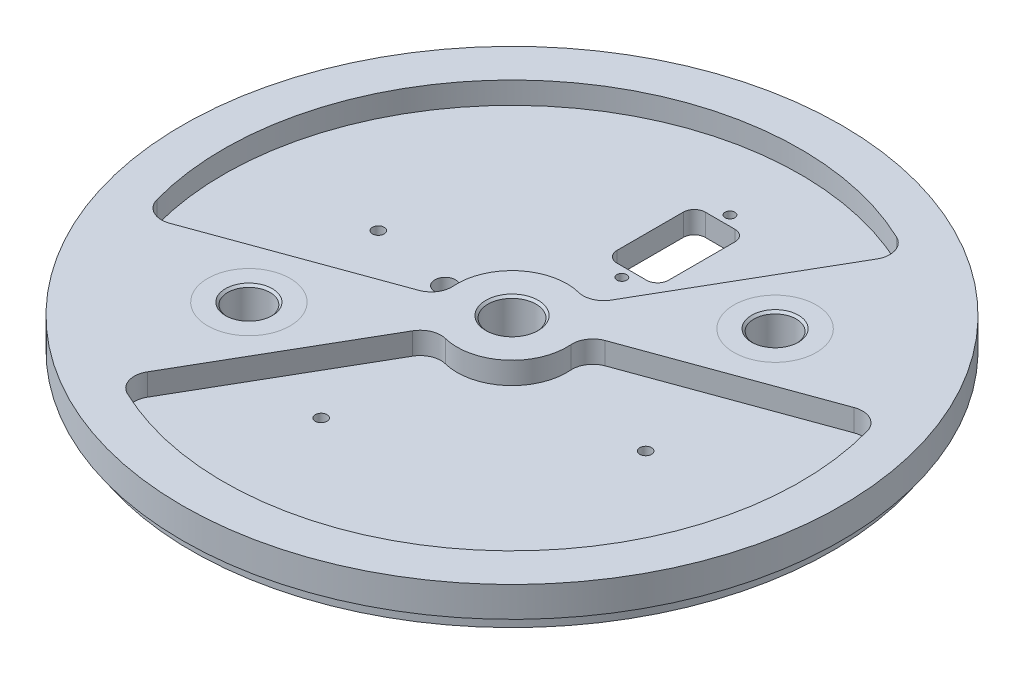
SolidWorks part; units mm, degrees
material "Delrin 2700 NC010, Low Viscosity Acetal Copolymer (SS)"
ref_plane "Front Plane" through (0, 0, 0) normal (0, 0, 1) x (1, 0, 0)
ref_plane "Top Plane" through (0, 0, 0) normal (0, 1, 0) x (1, 0, 0)
ref_plane "Right Plane" through (0, 0, 0) normal (1, 0, 0) x (0, 0, -1)
sketch "Sketch1" plane through (0, 0, 0) normal (0, 1, 0) x (1, 0, 0)
  circle A0 centre (0, 0) radius 76.2
  dimension "D1" = 152.4
extrude "Boss-Extrude1" add sketch "Sketch1" along normal blind 10.16
hole_wizard "Tap Drill for #4-40 Tap1" positions "Sketch3" profile "Sketch4" hole size "#4-40" standard "ANSI Inch" end condition through all
sketch "Sketch3" plane through (0, 0, 0) normal (0, -1, 0) x (-1, 0, 0)
  point P0 (0, 25.4)
  point P2 (0, 50.4)
  dimension "D1" = 25.4
  dimension "D2" = 25
sketch "Sketch4" plane through (0, 0, -25.4) normal (1, 0, 0) x (0, 0, -1)
  line L0 (0, 0) -> (0, 10.16)
  line L1 (0, 10.16) -> (1.1303, 10.16)
  line L2 (1.1303, 10.16) -> (1.1303, 0)
  line L5 (1.1303, 0) -> (0, 0)
  line L11 (0, -6.35) -> (0, 107.95) construction
  dimension "Thru Hole Dia." = 2.2606
  dimension "Thru Hole Depth" = 10.16
sketch "Sketch2" plane through (0, 0, 0) normal (0, -1, 0) x (1, 0, 0)
  line L0 (0, 0) -> (0, -55.372) construction
  line L1 (-3.429, -27.686) -> (3.429, -27.686)
  line L2 (-5.969, -30.226) -> (-5.969, -45.574)
  line L3 (-3.429, -48.114) -> (3.429, -48.114)
  line L4 (5.969, -30.226) -> (5.969, -45.574)
  arc A0 (3.429, -48.114) -> (5.969, -45.574) centre (3.429, -45.574) ccw
  arc A1 (-5.969, -45.574) -> (-3.429, -48.114) centre (-3.429, -45.574) ccw
  arc A2 (3.429, -27.686) -> (5.969, -30.226) centre (3.429, -30.226) cw
  arc A3 (-3.429, -27.686) -> (-5.969, -30.226) centre (-3.429, -30.226) ccw
  circle A4 centre (0, -25.4) radius 1.1303 construction
  circle A5 centre (0, -50.4) radius 1.1303 construction
  point P10 (5.969, -27.686)
  point P13 (-5.969, -27.686)
  point P17 (0, -27.686)
  dimension "D2" = 2.54
  dimension "D1" = 11.938
  dimension "D3" = 2.286
  dimension "D4" = 2.286
extrude "Cut-Extrude1" cut sketch "Sketch2" against normal through all
hole_wizard "Tap Drill for #6-32 Tap1" positions "Sketch5" profile "Sketch6" hole size "#6-32" standard "ANSI Inch" end condition through all
sketch "Sketch5" plane through (0, 0, 0) normal (0, -1, 0) x (-1, 0, 0)
  line L0 (0, 0) -> (58.3519, 0) construction
  line L2 (0, 0) -> (37.5212, 6.616) construction
  point P0 (37.5212, 6.616)
  dimension "D1" = 10
  dimension "D2" = 38.1
sketch "Sketch6" plane through (-37.5212, 0, -6.616) normal (1, 0, 0) x (0, 0, -1)
  line L0 (0, 0) -> (0, 10.16)
  line L1 (0, 10.16) -> (1.3525, 10.16)
  line L2 (1.3525, 10.16) -> (1.3525, 0)
  line L5 (1.3525, 0) -> (0, 0)
  line L11 (0, -6.35) -> (0, 107.95) construction
  dimension "Thru Hole Dia." = 2.7051
  dimension "Thru Hole Depth" = 10.16
pattern_circular "CirPattern1" count 4 over 360 about axis through (0, 0, 0) along (0, 1, 0) skipping 3 of "Tap Drill for #6-32 Tap1"
hole_wizard "W (0.386) Diameter Hole1" positions "Sketch7" profile "Sketch8" hole size "W" standard "ANSI Inch" end condition through all
sketch "Sketch7" plane through (0, 0, 0) normal (0, -1, 0) x (-1, 0, 0)
  line L2 (0, 0) -> (-33.0778, 27.7556) construction
  line L4 (0, 0) -> (0, 19.4817) construction
  point P0 (-33.0778, 27.7556)
  point P17 (33.0778, -27.7556)
  dimension "D1" = 50
  dimension "D2" = 43.18
  dimension "D3" = 43.18
sketch "Sketch8" plane through (33.0778, 0, -27.7556) normal (1, 0, 0) x (0, 0, -1)
  line L0 (0, 0) -> (0, 10.16)
  line L1 (0, 10.16) -> (4.9022, 10.16)
  line L2 (4.9022, 10.16) -> (4.9022, 0)
  line L5 (4.9022, 0) -> (0, 0)
  line L11 (0, -6.35) -> (0, 107.95) construction
  dimension "Thru Hole Dia." = 9.8044
  dimension "Thru Hole Depth" = 10.16
hole_wizard "3/16 (0.1875) Diameter Hole1" positions "Sketch10" profile "Sketch11" hole size "3/16" standard "ANSI Inch" end condition through all
sketch "Sketch10" plane through (0, 0, 0) normal (0, -1, 0) x (-1, 0, 0)
  line L0 (0, 0) -> (37.5212, 6.616) construction
  point P0 (18.7606, 3.308)
sketch "Sketch11" plane through (-18.7606, 0, -3.308) normal (1, 0, 0) x (0, 0, -1)
  line L0 (0, 0) -> (0, 10.16)
  line L1 (0, 10.16) -> (2.3812, 10.16)
  line L2 (2.3812, 10.16) -> (2.3812, 0)
  line L5 (2.3812, 0) -> (0, 0)
  line L11 (0, -6.35) -> (0, 107.95) construction
  dimension "Thru Hole Dia." = 4.7625
  dimension "Thru Hole Depth" = 10.16
sketch "Sketch12" plane through (0, 0, 0) normal (0, -1, 0) x (1, 0, 0)
  line L0 (0, 0) -> (31.6547, 37.7246) construction
  line L10 (19.8869, 28.7385) -> (24.8486, 24.5751)
  line L11 (19.8869, 28.7385) -> (6.4989, 12.7833)
  line L12 (6.4989, 12.7833) -> (11.4606, 8.62)
  line L13 (24.8486, 24.5751) -> (11.4606, 8.62)
  line L17 (0, 0) -> (-53.1972, 0) construction
  line L18 (-33.0778, 27.7556) -> (33.0778, -27.7556) construction
  circle A0 centre (22.3677, 26.6568) radius 3.2385
  circle A1 centre (8.9797, 10.7016) radius 3.2385
  circle A2 centre (33.0778, -27.7556) radius 4.9022 construction
  circle A3 centre (-33.0778, 27.7556) radius 4.9022 construction
  circle A4 centre (33.0778, -27.7556) radius 4.9022
  circle A5 centre (-33.0778, 27.7556) radius 4.9022
  dimension "D1" = 6.477
  dimension "D2" = 13.97
  dimension "D3" = 20.828
extrude "Cut-Extrude4" cut sketch "Sketch12" against normal blind 3.175 contours A1 L13 A0 L11 | L10 A0 | L12 A1 | L12 A1 | L10 A0 region at (23.2512, 0, 27.7097) region at (15.6737, 0, 18.6792) region at (21.4842, 0, 25.6039) region at (9.8632, 0, 11.7545) region at (8.0963, 0, 9.6487)
ref_plane "Plane1" through (0, 0, 0) normal (0.6428, 0, 0.766) x (0.766, 0, -0.6428)
mirror "Mirror1" about plane through (0, 0, 0) normal (0.6428, 0, 0.766) of "Cut-Extrude4"
hole_wizard "7/16 (0.4375) Diameter Hole1" positions "Sketch13" profile "Sketch14" hole size "7/16" standard "ANSI Inch" end condition through all
sketch "Sketch13" plane through (0, 0, 0) normal (0, -1, 0) x (-1, 0, 0)
  point P0 (0, 0)
sketch "Sketch14" plane through (0, 0, 0) normal (1, 0, 0) x (0, 0, -1)
  line L0 (0, 0) -> (0, 10.16)
  line L1 (0, 10.16) -> (5.5562, 10.16)
  line L2 (5.5562, 10.16) -> (5.5562, 0)
  line L5 (5.5562, 0) -> (0, 0)
  line L11 (0, -6.35) -> (0, 107.95) construction
  dimension "Thru Hole Dia." = 11.1125
  dimension "Thru Hole Depth" = 10.16
sketch "Sketch15" plane through (0, 0, 0) normal (0, -1, 0) x (1, 0, 0)
  circle A0 centre (0, 0) radius 74.041
  circle A1 centre (0, 0) radius 76.2 construction
  circle A2 centre (0, 0) radius 76.2
  dimension "D1" = 148.082
extrude "Cut-Extrude5" cut sketch "Sketch15" against normal blind 3.175
sketch "Sketch17" plane through (0, 10.16, 0) normal (0, 1, 0) x (1, 0, 0)
  circle A0 centre (-33.0778, -27.7556) radius 9.525
  circle A1 centre (33.0778, 27.7556) radius 9.525
  dimension "D1" = 19.05
  dimension "D2" = 19.05
split line "Split Line1"
sketch "Sketch19" plane through (0, 0, 0) normal (0, -1, 0) x (1, 0, 0)
  circle A0 centre (-33.0778, 27.7556) radius 9.525
  circle A1 centre (33.0778, -27.7556) radius 9.525
  dimension "D1" = 19.05
  dimension "D2" = 19.05
split line "Split Line2"
chamfer "Chamfer2" distance 0.508 angle 45 6 edges at (-33.0778, 0, 22.8534) (33.0778, 0, -32.6578) (-33.0778, 10.16, 22.8534) (33.0778, 10.16, -32.6578) (0, 0, -5.5562) (0, 10.16, -5.5562)
sketch "Sketch18" plane through (0, 10.16, 0) normal (0, 1, 0) x (1, 0, 0)
  circle A0 centre (0, 0) radius 76.2 construction
  circle A1 centre (33.0778, 27.7556) radius 9.525 construction
  circle A2 centre (-33.0778, -27.7556) radius 9.525 construction
  circle A3 centre (0, 0) radius 76.2
  circle A4 centre (33.0778, 27.7556) radius 9.525
  circle A5 centre (-33.0778, -27.7556) radius 9.525
  circle A7 centre (0, 0) radius 12.7
  circle A8 centre (-18.7606, 3.308) radius 9.525
  dimension "D1" = 25.4
  dimension "D2" = 19.05
extrude "Cut-Extrude6" [suppressed] cut sketch "Sketch18" against normal blind 4.7625
sketch "Sketch20" plane through (0, 10.16, 0) normal (0, 1, 0) x (1, 0, 0)
  line L0 (-5.3508, -4.4899) -> (5.3508, 4.4899) construction
  line L1 (11.9341, 4.3437) -> (62.654, 22.8042)
  line L2 (0, 0) -> (-85.2847, -31.0411) construction
  line L3 (0, 0) -> (40.2406, 69.6988) construction
  line L4 (0, 0) -> (-109.7287, 0) construction
  line L5 (6.35, 10.9985) -> (33.3375, 57.7422)
  line L6 (-62.654, -22.8042) -> (-11.9341, -4.3437)
  line L7 (-33.3375, -57.7422) -> (-6.35, -10.9985)
  circle A0 centre (0, 0) radius 66.675
  circle A1 centre (0, 0) radius 12.7
  circle A2 centre (-59.6352, -16.6373) radius 4.7625
  circle A4 centre (26.7401, 55.8402) radius 4.7625
  circle A7 centre (4.2758, 16.9309) radius 4.7625
  circle A8 centre (-17.4162, -1.2708) radius 4.7625
  circle A9 centre (-4.2758, -16.9309) radius 4.7625
  circle A10 centre (17.4162, 1.2708) radius 4.7625
  circle A11 centre (59.6352, 16.6373) radius 4.7625
  circle A12 centre (-26.7401, -55.8402) radius 4.7625
  point P15 (-11.9341, -4.3437)
  point P17 (0, 0)
  point P24 (-61.2746, -8.8644)
  point P26 (-62.654, -22.8042)
  point P27 (-60.6031, -12.7)
  point P30 (12.7, 36.9438)
  point P33 (-38.1916, 16.3456)
  circle M14 centre (-18.7606, 3.308) radius 2.3812
  circle M15 centre (37.5212, -6.616) radius 1.3526
  circle M16 centre (-6.616, -37.5212) radius 1.3525
  circle M17 centre (-37.5212, 6.616) radius 1.3526
  arc M18 (3.429, 48.114) -> (5.969, 45.574) centre (3.429, 45.574) cw
  line M19 (5.969, 45.574) -> (5.969, 30.226)
  arc M20 (5.969, 30.226) -> (3.429, 27.686) centre (3.429, 30.226) cw
  line M21 (3.429, 27.686) -> (-3.429, 27.686)
  arc M22 (-3.429, 27.686) -> (-5.969, 30.226) centre (-3.429, 30.226) cw
  line M23 (-5.969, 30.226) -> (-5.969, 45.574)
  arc M24 (-5.969, 45.574) -> (-3.429, 48.114) centre (-3.429, 45.574) cw
  line M25 (-3.429, 48.114) -> (3.429, 48.114)
  circle M26 centre (0, 25.4) radius 1.1303
  circle M27 centre (0, 50.4) radius 1.1303
  dimension "D1" = 133.35
  dimension "D2" = 25.4
  dimension "D4" = 9.525
  dimension "D3" = 20
  dimension "D5" = 140
extrude "Cut-Extrude7" cut sketch "Sketch20" against normal blind 5.08 contours A8 A1 A7 L5 A4 A0 A2 L6 M14 M25 M18 M19 M20 M21 M22 M23 M24 M26 M27 M17 | A7 | A4 | A8 M14 | A2 | L7 A12 A0 A11 L1 A10 A1 A9 M16 M15 | A9 | A10 | A11 | A12 region at (23.3482, 10.16, 27.8168) region at (17.4162, 10.16, -1.2708) region at (59.6352, 10.16, -16.6373) region at (-24.5522, 10.16, -27.347) region at (4.2758, 10.16, -16.9309) region at (26.7401, 10.16, -55.8402) region at (-17.2875, 10.16, 1.7091) region at (-4.2758, 10.16, 16.9309) region at (-26.7401, 10.16, 55.8402) region at (-59.6352, 10.16, 16.6373)
equation "\"Bodytube_OD\" = 6.17in"
equation "\"Bodytube_ID\" = 5.998in"
equation "\"Camera_Cutout_Width\"=10mm"
equation "\"Camera_Cutout_Height\"=7mm"
equation "\"Fwd_Tube_Length\" = 40in"
equation "\"BKHD_Screw_Diam\"= 3.5mm"
equation "\"Fwd_BKHD_From_Top\" = 18in"
equation "\"Shear_Screw_Diameter\" = 0.086in"
equation "\"Shear_Screw_Coupler_Location\" = 4.5in"
equation "\"Motor_OD\" = 4in"
equation "\"Mid_Coupler_Length\" = 13in"
equation "\"Aft_Section_Length\"= 39in"
equation "\"AB_Coupler_OD_Length\"= 1in"
equation "\"AB_Coupling_Section_Length\"= 0.375in"
equation "\"AB_Coupler_Length\"= \"AB_Coupler_OD_Length\" + \"AB_Coupling_Section_Length\" * 2"
equation "\"Cutout_Angle\" = 80"
equation "\"AB_Paddle_Height\" = 0.375in"
equation "\"AB_Coupler_Num_Screws\"= 4"
equation "\"AB_BKHD_Thickness\" = 0.375in"
equation "\"AB_Mount_From_Bottom\" = 23.175in"
equation "\"Num_Cutouts\" = 3"
equation "\"AB_Coupler_OD\"= 6.17in"
equation "\"AB_Coupler_ID\"= 5.75in"
equation "\"AB_Coupler_Surface_Diameter\"= 5.998in"
equation "\"AB_Coupling_Screw_Diameter\"= 0.15748in"
equation "\"AB_Central_Bushing_Length\" = .4724in"
equation "\"Lead_Screw_Dist\" = 3.4in"
equation "\"Lead_Screw_Diam\" = 0.386in"
equation "\"Lead_Screw_Length\" = (\"Mid_Coupler_Length\" + 2*0.375in + 2*0.5in)"
equation "\"Paddle_Pin_Offset\" = .25in"
equation "\"Paddle_Pin_Radius\" = 2.25in"
equation "\"SS_Paddle_Pin_Radius\" = 2.25*0.66in"
equation "\"Paddle_Gear_OD\" = 3.2in"
equation "\"Drive_Gear_OD\" = 1.7in"
equation "\"Fin_Thickness\"= .118in"
equation "\"Guiderail_Cutout_Diameter\"= 1.5in"
equation "\"DB9_Hole_Dist\" = 25mm"
equation "\"DB9_Relief_Width\" = 0.47in"
equation "\"DB9_Relief_Hole_Offset\" = 0.09in"
equation "\"Airbrakes_Wire_Hole_Dia\" = .25in"
equation "\"Airbrakes_Wire_Hole_Dist\" = 1.1in"
equation "\"Servo_Gear_Offset\" = 0.5in"
equation "\"FWD_Shear_Screw_Dist\" = 1.5in"
equation "\"Camera_Screw_Dia\" = 0.216535"
equation "\"Camera_Hole_Angle\" = atn ( 2 / 3 * tan ( 12.5deg ) )"
equation "\"Coupler_OD\" = 5.998"
equation "\"Coupler_ID\" = 5.8"
equation "\"Mounting_Bracket_Centerhole_DIA\" = 0.4in"
equation "\"Drive_Gear_Shaft_DIA\" = \"Mounting_Bracket_Centerhole_DIA\" - 0.02in"
equation "\"Drive_Gear_Fillet\" = 0.22in"
equation "\"Drive_Gear_ID\" = 0.62in"
equation "\"Drive_Gear_Offset\" = 0.01in"
equation "\"D1@Sketch2\"=\"DB9_Relief_Width\""
equation "\"D2@Sketch3\"=\"DB9_Hole_Dist\""
equation "\"D3@Sketch2\"=\"DB9_Relief_Hole_Offset\""
equation "\"D4@Sketch2\"=\"DB9_Relief_Hole_Offset\""
equation "\"D2@Sketch7\"=\"Lead_Screw_Dist\"/2"
equation "\"D3@Sketch7\"=\"Lead_Screw_Dist\"/2"
